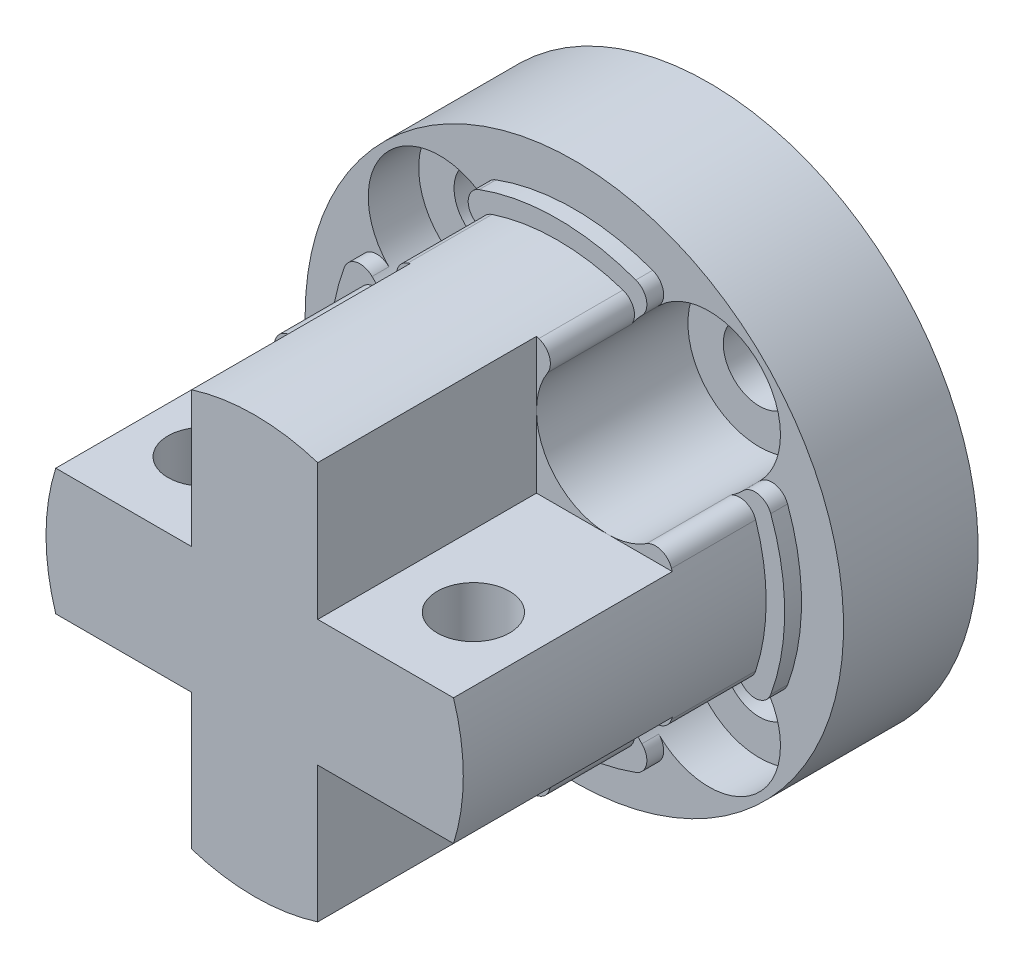
SolidWorks part; units mm, degrees
ref_plane "Front Plane" through (0, 0, 0) normal (0, 0, 1) x (1, 0, 0)
ref_plane "Top Plane" through (0, 0, 0) normal (0, 1, 0) x (1, 0, 0)
ref_plane "Right Plane" through (0, 0, 0) normal (1, 0, 0) x (0, 0, -1)
sketch "Sketch1" plane through (0, 0, 0) normal (0, 1, 0) x (1, 0, 0)
  line L0 (0, 0) -> (16, 0)
  line L1 (16, 0) -> (16, -8)
  line L2 (16, -8) -> (12.4, -8)
  line L3 (12.4, -8) -> (12.4, -14)
  line L4 (12.4, -14) -> (2.7, -14)
  line L5 (2.7, -14) -> (2.7, 0)
  line L6 (0, 0) -> (0, -14) construction
  line L7 (2.7, -14) -> (0, -14)
  line L8 (0, -14) -> (0, -12)
  line L9 (0, -12) -> (2.7, -12)
  dimension "D1" = 16
  dimension "D2" = 12.4
  dimension "D3" = 8
  dimension "D4" = 6
  dimension "D5" = 2.7
  dimension "D6" = 2
revolve "Revolve1" add sketch "Sketch1" angle 360 about L6 region at (8.7135, 0, 6.4751) region at (1.35, 0, 13)
sketch "Sketch2" plane through (0, 0, 8) normal (0, 0, 1) x (1, 0, 0)
  circle A0 centre (-8, 8) radius 2.15
  circle A1 centre (-8, 8) radius 4.25
  circle A2 centre (8, 8) radius 4.25
  circle A3 centre (8, 8) radius 2.15
  circle A4 centre (8, -8) radius 4.25
  circle A5 centre (8, -8) radius 2.15
  circle A6 centre (-8, -8) radius 4.25
  circle A7 centre (-8, -8) radius 2.15
  circle A8 centre (0, 0) radius 2.7 construction
  point P16 (0, 0)
  circle M3 centre (0, 0) radius 12.4
  dimension "D1" = 4.3
  dimension "D2" = 8.5
  dimension "D3" = 8
  dimension "D4" = 8
  dimension "D5" = 4
extrude "Cut-Extrude1" cut sketch "Sketch2" against normal through all both and the other way through all contours A0 M3 | A7 M3 | A7 M3 | A0 M3 | A3 M3 | A3 M3 | A5 M3 | A5 M3 region at (-7.7274, 7.7274, 8) region at (-9.0554, 9.0554, 8) region at (7.7274, 7.7274, 8) region at (9.0554, 9.0554, 8) region at (-9.0554, -9.0554, 8) region at (-7.7274, -7.7274, 8) region at (9.0554, -9.0554, 8) region at (7.7274, -7.7274, 8)
extrude "Cut-Extrude3" cut sketch "Sketch2<4>" along normal through all and the other way blind 3 contours A1 A0 M3 | A7 A6 M3 | A3 A2 M3 | A5 A4 M3 | A1 A0 M3 | A3 A2 M3 | A5 A4 M3 | A7 A6 M3 region at (-6.1606, 9.306, 8) region at (-9.6852, 9.6852, 8) region at (6.2433, 10.5909, 8) region at (9.6852, 9.6852, 8) region at (-9.6852, -9.6852, 8) region at (-6.5687, -4.1109, 8) region at (9.6852, -9.6852, 8) region at (5.0697, -5.0697, 8)
sketch "Sketch2<4>" plane through (0, 0, 8) normal (0, 0, 1) x (1, 0, 0) same geometry as "Sketch2"
sketch "Sketch3" plane through (0, 0, 8) normal (0, 0, 1) x (1, 0, 0)
  circle A0 centre (0, 0) radius 13.5
  circle A1 centre (8, 8) radius 4.25
  circle A2 centre (8, -8) radius 4.25
  circle A3 centre (-8, -8) radius 4.25
  arc M2 (-5.245, -11.2361) -> (-11.2361, -5.245) centre (-8, -8) cw
  arc M3 (-11.2361, -5.245) -> (-11.2361, 5.245) centre (0, 0) cw
  arc M4 (-11.2361, 5.245) -> (-5.245, 11.2361) centre (-8, 8) cw
  arc M5 (-5.245, 11.2361) -> (5.245, 11.2361) centre (0, 0) cw
  arc M6 (5.245, 11.2361) -> (11.2361, 5.245) centre (8, 8) cw
  arc M7 (11.2361, 5.245) -> (11.2361, -5.245) centre (0, 0) cw
  arc M8 (11.2361, -5.245) -> (5.245, -11.2361) centre (8, -8) cw
  arc M9 (5.245, -11.2361) -> (-5.245, -11.2361) centre (0, 0) cw
  dimension "D1" = 27
extrude "Boss-Extrude1" add sketch "Sketch3" along normal blind 1 contours A0 M6 M4 M5 | A0 M4 M2 M3 | A0 M2 M8 M9 | A0 M8 M6 M7 region at (12.5109, 0, 8) region at (0, 12.5109, 8) region at (0, -12.5109, 8) region at (-12.5109, 0, 8)
sketch "Sketch4" plane through (0, 0, 14) normal (0, 0, 1) x (1, 0, 0)
  line L0 (-11.8194, 3.75) -> (11.8194, 3.75)
  line L1 (-11.8194, -3.75) -> (11.8194, -3.75)
  line L2 (-3.75, 11.8194) -> (-3.75, -11.8194)
  line L3 (3.75, 11.8194) -> (3.75, -11.8194)
  arc A0 (-11.2361, 5.245) -> (-11.2361, -5.245) centre (0, 0) ccw construction
  arc A1 (11.2361, -5.245) -> (11.2361, 5.245) centre (0, 0) ccw construction
  arc A2 (-11.2361, 5.245) -> (-11.2361, -5.245) centre (0, 0) ccw construction
  circle A3 centre (-8, 8) radius 4.25 construction
  circle A4 centre (-8, -8) radius 4.25 construction
  arc A5 (5.245, 11.2361) -> (-5.245, 11.2361) centre (0, 0) ccw construction
  arc A6 (-5.245, -11.2361) -> (5.245, -11.2361) centre (0, 0) ccw construction
  arc A7 (-5.245, -11.2361) -> (5.245, -11.2361) centre (0, 0) ccw construction
  circle A8 centre (8, -8) radius 4.25 construction
  arc A9 (-5.245, -11.2361) -> (-11.2361, -5.245) centre (-8, -8) ccw construction
  circle A10 centre (0, 0) radius 12.4
  arc M7 (-5.245, -11.2361) -> (5.245, -11.2361) centre (0, 0) ccw
  arc M9 (11.2361, -5.245) -> (11.2361, 5.245) centre (0, 0) ccw
  arc M11 (5.245, 11.2361) -> (-5.245, 11.2361) centre (0, 0) ccw
  arc M13 (-11.2361, 5.245) -> (-11.2361, -5.245) centre (0, 0) ccw
extrude "Boss-Extrude2" add sketch "Sketch4" along normal blind 13 contours L3 L2 L0 M11 | L3 L0 L2 L1 | L2 L0 L1 M13 | L3 L1 L2 M7 | L0 L3 L1 M9 region at (-7.9809, 0, 14) region at (0, 7.9809, 14) region at (0, 0, 14) region at (7.9809, 0, 14) region at (0, -7.9809, 14)
fillet "Fillet1" radius 1 8 edges at (-11.2361, -5.245, 11.5) (-5.245, -11.2361, 11.5) (5.245, -11.2361, 11.5) (11.2361, -5.245, 11.5) (11.2361, 5.245, 11.5) (5.245, 11.2361, 11.5) (-11.2361, 5.245, 11.5) (-5.245, 11.2361, 11.5)
fillet "Fillet2" radius 1 8 edges at (-11.9152, -6.3465, 8.5) (-6.3465, -11.9152, 8.5) (6.3465, -11.9152, 8.5) (11.9152, -6.3465, 8.5) (11.9152, 6.3465, 8.5) (6.3465, 11.9152, 8.5) (-11.9152, 6.3465, 8.5) (-6.3465, 11.9152, 8.5)
sketch "Sketch5" plane through (0, 3.75, 0) normal (0, 1, 0) x (1, 0, 0)
  line L0 (3.75, -27) -> (11.8194, -27) construction
  circle A0 centre (-8, -22) radius 2.15
  circle A1 centre (8, -22) radius 2.15
  dimension "D1" = 4.3
  dimension "D2" = 4.3
  dimension "D3" = 8
  dimension "D4" = 8
  dimension "D5" = 5
extrude "Cut-Extrude4" cut sketch "Sketch5" against normal up to next
